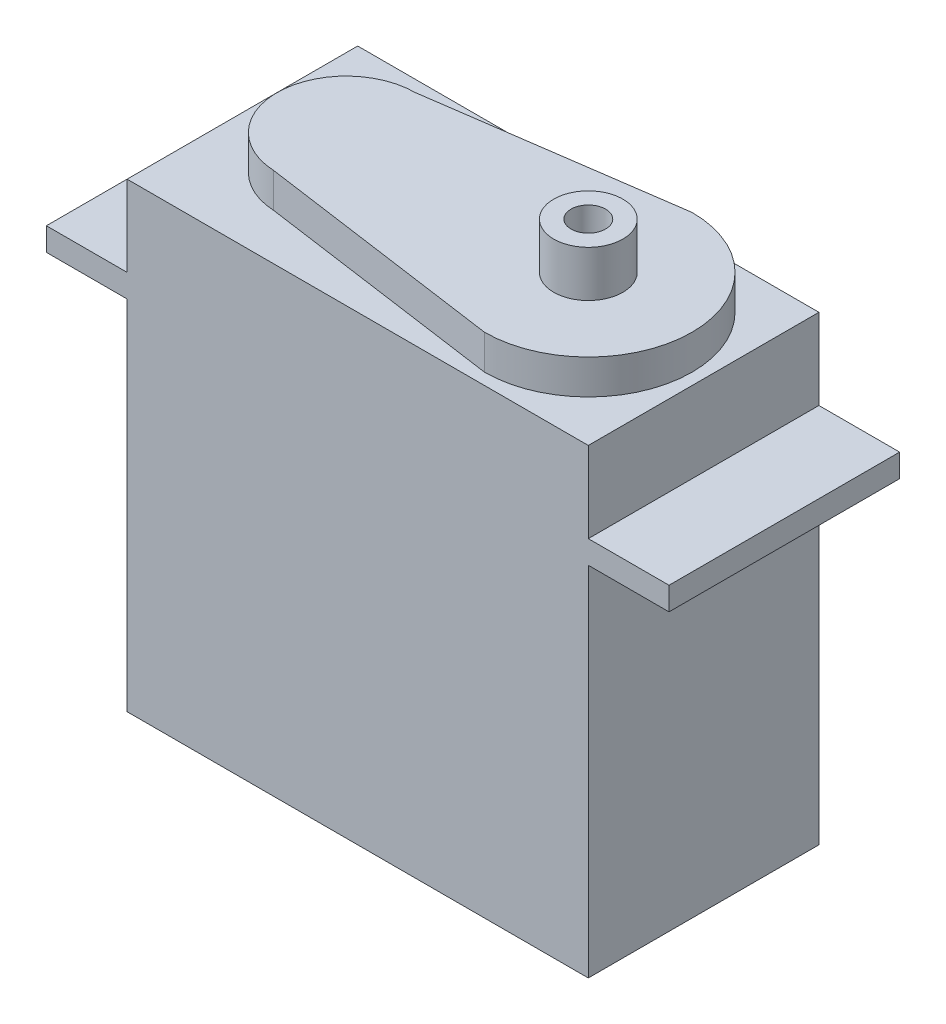
SolidWorks part; units mm, degrees
ref_plane "前视基准面" through (0, 0, 0) normal (0, 0, 1) x (1, 0, 0)
ref_plane "上视基准面" through (0, 0, 0) normal (0, 1, 0) x (1, 0, 0)
ref_plane "右视基准面" through (0, 0, 0) normal (1, 0, 0) x (0, 0, -1)
sketch "草图1" plane through (0, 0, 0) normal (0, 0, 1) x (1, 0, 0)
  line L1 (-20, 20) -> (20, 20)
  line L2 (-20, 20) -> (-20, -20)
  line L3 (-20, -20) -> (20, -20)
  line L4 (20, 20) -> (20, -20)
  line L5 (-20, 20) -> (20, -20) construction
  line L6 (-20, -20) -> (20, 20) construction
  point P0 (0, 0)
  dimension "D1" = 40
  dimension "D2" = 40
extrude "凸台-拉伸1" add sketch "草图1" along normal blind 20
sketch "草图2" plane through (0, 20, 0) normal (0, 1, 0) x (1, 0, 0)
  line L3 (20, -20) -> (20, 0) construction
  line L4 (-20, -20) -> (-20, 0) construction
  line L5 (10, -1) -> (-11, -4)
  line L6 (-11.2901, -15.993) -> (10, -19)
  arc A0 (10, -19) -> (10, -1) centre (10, -10) ccw
  arc A1 (-11, -4) -> (-11.2901, -15.993) centre (-11, -10) ccw
  point P7 (19, -10)
  point P10 (10, -10)
  point P13 (-17, -10)
  point P16 (-11, -10)
  dimension "D2" = 1
  dimension "D3" = 9
  dimension "D4" = 3
  dimension "D5" = 6
extrude "凸台-拉伸2" add sketch "草图2" along normal blind 3 contours L5 A1 L6 A0
sketch "草图5" plane through (0, 23, 0) normal (0, 1, 0) x (1, 0, 0)
  line L0 (-23.0759, -10) -> (28.1102, -10) construction
  line L1 (20, 0) -> (-20, 0) construction
  line L2 (20, -20) -> (20, 0) construction
  circle A0 centre (10, -10) radius 3
  circle A1 centre (10, -10) radius 1.5
  point P4 (10, -10)
  dimension "D1" = 10
  dimension "D2" = 10
extrude "凸台-拉伸3" add sketch "草图5" along normal blind 4
sketch "草图6" plane through (0, 0, 0) normal (0, 0, -1) x (-1, 0, 0)
  line L0 (-20, -20) -> (-20, 20) construction
  line L1 (-20, 13) -> (-27, 13)
  line L2 (-20, 13) -> (-20, 11)
  line L3 (-20, 11) -> (-27, 11)
  line L4 (-27, 13) -> (-27, 11)
  line L5 (-20, 20) -> (20, 20) construction
  line L6 (20, 20) -> (20, -20) construction
  line L7 (20, 13) -> (27, 13)
  line L8 (20, 13) -> (20, 11)
  line L9 (20, 11) -> (27, 11)
  line L10 (27, 13) -> (27, 11)
  dimension "D1" = 7
  dimension "D2" = 7
  dimension "D3" = 2
  dimension "D4" = 7
  dimension "D5" = 2
  dimension "D6" = 7
extrude "凸台-拉伸4" add sketch "草图6" against normal blind 20
ref_axis "基准轴Sevo" through (10, 27, 10) along (0, -1, 0)
sketch "草图7" plane through (0, 27, 0) normal (0, 1, 0) x (1, 0, 0)
  line L0 (-0.7099, -10) -> (20.7099, -10)
  line L1 (10, -0.6903) -> (10, -19.3097)
  point P4 (10, -10)
  point P7 (10, -10)
